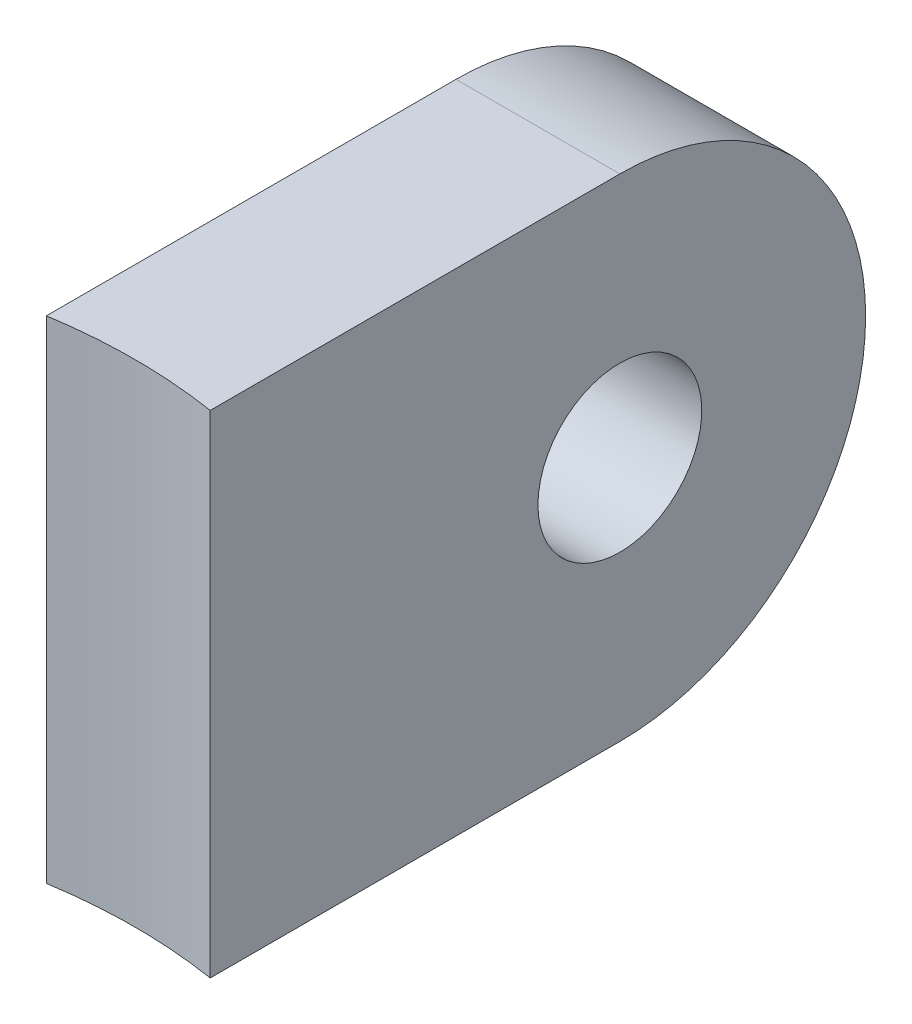
SolidWorks part; units mm, degrees
ref_plane "Front Plane" through (0, 0, 0) normal (0, 0, 1) x (1, 0, 0)
ref_plane "Top Plane" through (0, 0, 0) normal (0, 1, 0) x (1, 0, 0)
ref_plane "Right Plane" through (0, 0, 0) normal (1, 0, 0) x (0, 0, -1)
sketch "Sketch1" plane through (0, 0, 0) normal (0, 1, 0) x (1, 0, 0)
  line L0 (-2.5, 15.6769) -> (-2.5, 35.6769)
  line L1 (-2.5, 35.6769) -> (2.5, 35.6769)
  line L2 (2.5, 35.6769) -> (2.5, 15.6769)
  arc A0 (2.5, 15.6769) -> (-2.5, 15.6769) centre (0, 0) ccw
  dimension "D1" = 31.75
  dimension "D2" = 20
  dimension "D3" = 5
  dimension "D4" = 2.5
extrude "Boss-Extrude1" add sketch "Sketch1" along normal blind 15
fillet "Fillet1" radius 7.5 2 edges at (0, 0, -35.6769) (0, 15, -35.6769)
sketch "Sketch2" plane through (-2.5, 0, 0) normal (-1, 0, 0) x (0, 0, 1)
  circle A0 centre (-28.1769, 7.5) radius 2.5
  dimension "D1" = 5
extrude "Cut-Extrude1" cut sketch "Sketch2" against normal through all
